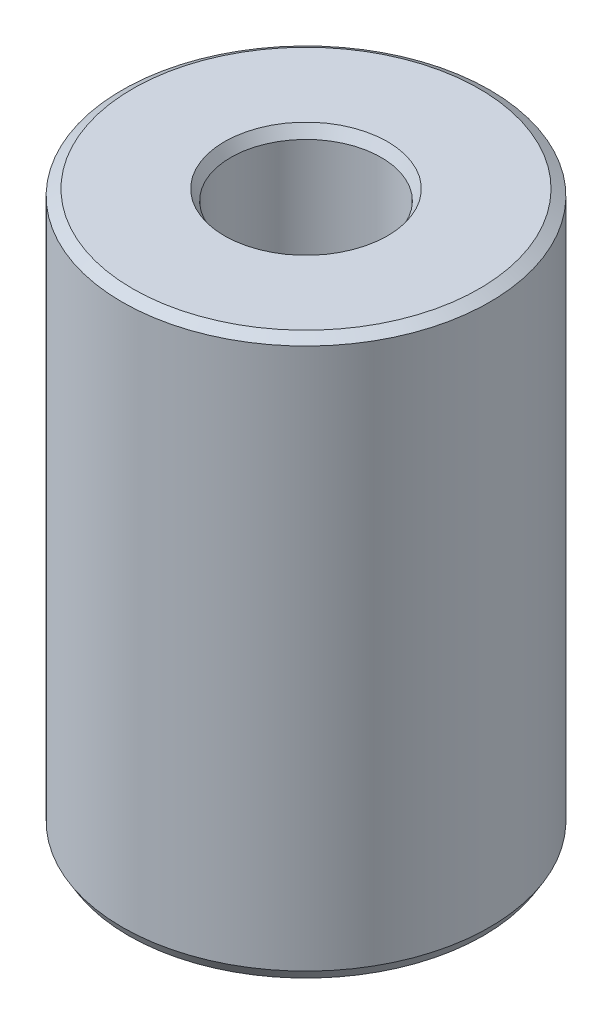
SolidWorks part; units mm, degrees
ref_plane "Front Plane" through (0, 0, 0) normal (0, 0, 1) x (1, 0, 0)
ref_plane "Top Plane" through (0, 0, 0) normal (0, 1, 0) x (1, 0, 0)
ref_plane "Right Plane" through (0, 0, 0) normal (1, 0, 0) x (0, 0, -1)
sketch "Sketch1" plane through (0, 0, 0) normal (0, 1, 0) x (1, 0, 0)
  circle A0 centre (0, 0) radius 17.5
  dimension "SLEEVE_OD" = 35
extrude "Boss-Extrude1" add sketch "Sketch1" along normal blind 53.1471
sketch "Sketch2" plane through (0, 0, 0) normal (0, 1, 0) x (1, 0, 0)
  circle A0 centre (0, 0) radius 7.1665
  dimension "BORE_D" = 14.333
extrude "Cut-Extrude1" cut sketch "Sketch2" along normal through all
chamfer "Chamfer1" distance 0.6007 angle 58.977 4 edges at (0, 53.1471, 7.1665) (0, 0, 7.1665) (0, 0, 17.5) (0, 53.1471, 17.5) first distance on face at (0, 53.1471, 7.1665) first distance on face at (0, 0, 7.1665) first distance on face at (0, 53.1471, 17.5)
